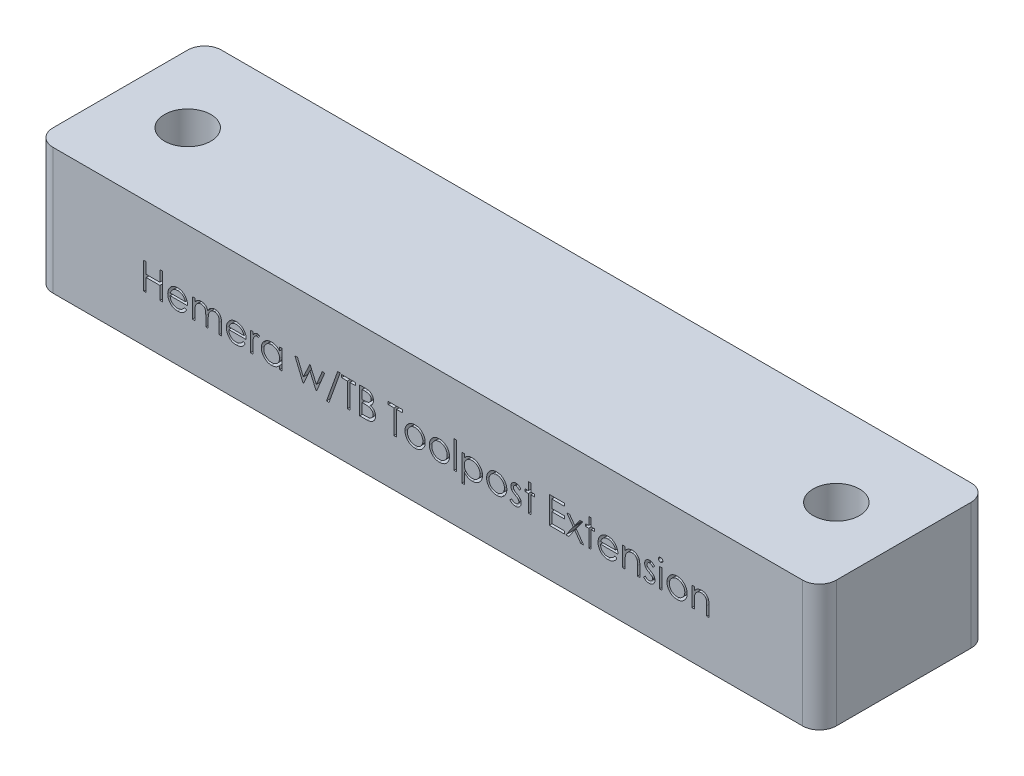
SolidWorks part; units mm, degrees
ref_plane "Front Plane" through (0, 0, 0) normal (0, 0, 1) x (1, 0, 0)
ref_plane "Top Plane" through (0, 0, 0) normal (0, 1, 0) x (1, 0, 0)
ref_plane "Right Plane" through (0, 0, 0) normal (1, 0, 0) x (0, 0, -1)
sketch "Sketch1" plane through (0, 0, 0) normal (0, 1, 0) x (1, 0, 0)
  line L0 (-44.5, -10) -> (44.5, -10)
  line L1 (46.5, -8) -> (46.5, 8)
  line L2 (44.5, 10) -> (-44.5, 10)
  line L3 (-46.5, 8) -> (-46.5, -8)
  arc A0 (44.5, -10) -> (46.5, -8) centre (44.5, -8) ccw
  arc A1 (46.5, 8) -> (44.5, 10) centre (44.5, 8) ccw
  arc A2 (-44.5, 10) -> (-46.5, 8) centre (-44.5, 8) ccw
  arc A3 (-46.5, -8) -> (-44.5, -10) centre (-44.5, -8) ccw
extrude "Boss-Extrude1" add sketch "Sketch1" along normal blind 15
hole_wizard "M5 Clearance Hole1" positions "Sketch2" profile "Sketch3" hole size "M5" standard "ANSI Metric" end condition through all
sketch "Sketch2" plane through (0, 15, 0) normal (0, 1, 0) x (1, 0, 0)
  line L0 (-44.5, -10) -> (44.5, -10) construction
  line L1 (46.5, -8) -> (46.5, 8) construction
  point P0 (38.5, 0)
  point P2 (-38.5, 0)
  dimension "D1" = 77
  dimension "D2" = 10
  dimension "D3" = 8
sketch "Sketch3" plane through (38.5, 15, 0) normal (1, 0, 0) x (0, 0, 1)
  line L0 (0, 0) -> (0, 15)
  line L1 (0, 15) -> (2.75, 15)
  line L2 (2.75, 15) -> (2.75, 0)
  line L5 (2.75, 0) -> (0, 0)
  line L11 (0, -6.35) -> (0, 107.95) construction
  dimension "Thru Hole Dia." = 5.5
  dimension "Thru Hole Depth" = 15
sketch "Sketch4" plane through (0, 0, 10) normal (0, 0, 1) x (1, 0, 0)
  line L0 (-34.1266, 5.5992) -> (33.994, 5.5992) construction
  text T0 "Hemera w/TB Toolpost Extension"
  point P0 (33.994, 4.6709)
  point P3 (-0.0663, 5.5992)
extrude "Cut-Extrude1" cut sketch "Sketch4" against normal blind 1
